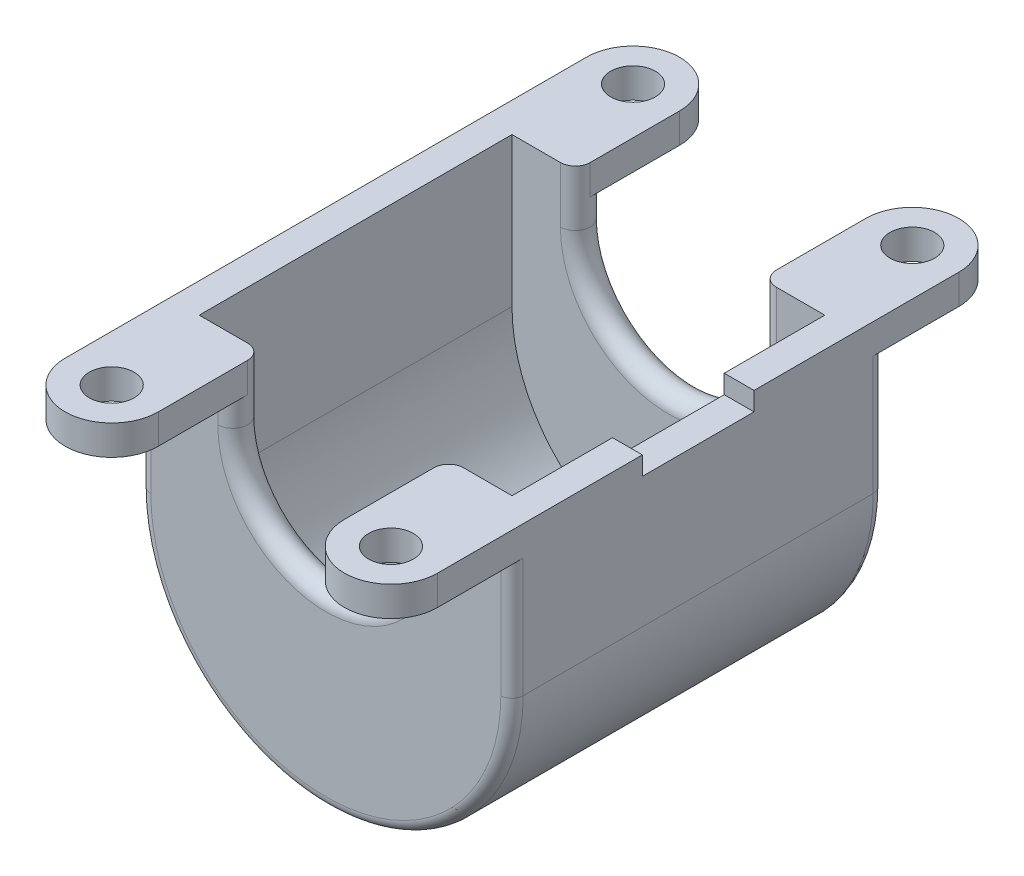
SolidWorks part; units mm, degrees
ref_plane "Alzado" through (0, 0, 0) normal (0, 0, 1) x (1, 0, 0)
ref_plane "Planta" through (0, 0, 0) normal (0, 1, 0) x (1, 0, 0)
ref_plane "Vista lateral" through (0, 0, 0) normal (1, 0, 0) x (0, 0, -1)
sketch "Croquis4" plane through (0, 0, 0) normal (0, 1, 0) x (1, 0, 0)
  line L0 (0, 0) -> (0, 140)
  line L1 (-25, 140) -> (-25, 120)
  line L2 (-25, 0) -> (-25, 20)
  line L3 (0, 70) -> (-100, 70) construction
  line L4 (-50, 70) -> (-50, 196) construction
  line L5 (-25, 120) -> (-75, 120)
  line L6 (-25, 20) -> (-75, 20)
  line L7 (-75, 0) -> (-75, 20)
  line L8 (-100, 0) -> (-100, 140)
  line L9 (-75, 140) -> (-75, 120)
  arc A0 (0, 140) -> (-25, 140) centre (-12.5, 140) ccw
  arc A1 (0, 0) -> (-25, 0) centre (-12.5, 0) cw
  arc A2 (-100, 0) -> (-75, 0) centre (-87.5, 0) ccw
  arc A3 (-100, 140) -> (-75, 140) centre (-87.5, 140) cw
  point P13 (0, 0)
  point P17 (-50, 20)
  point P24 (-50, 120)
  dimension "D2" = 12.5
  dimension "D1" = 140
  dimension "D3" = 100
  dimension "D4" = 50
  dimension "D5" = 50
extrude "Base" add sketch "Croquis4" along normal blind 8
sketch "Croquis5" plane through (0, 0, 0) normal (0, -1, 0) x (1, 0, 0)
  circle A0 centre (-87.5, 0) radius 6
  circle A1 centre (-12.5, 0) radius 6
  circle A2 centre (-87.5, -140) radius 6
  circle A3 centre (-12.5, -140) radius 6
  point P17 (-12.5, 0)
  point P21 (-87.5, -140)
  point P25 (-12.5, -140)
  dimension "D1" = 12
extrude "Perforaciones" cut sketch "Croquis5" against normal blind 8
ref_plane "Plano2" through (0, 0, -20) normal (0, 0, 1) x (1, 0, 0)
sketch "Croquis7" plane through (0, 0, -20) normal (0, 0, 1) x (1, 0, 0)
  line L1 (-100, 0) -> (-100, -32)
  line L2 (0, -32) -> (0, 0)
  line L4 (-50, -82) -> (-50, 14.9348) construction
  line L8 (-100, 0) -> (0, 0)
  arc A0 (-100, -32) -> (0, -32) centre (-50, -32) ccw
  dimension "D1" = 50
  dimension "D2" = 32
extrude "Saliente-Extruir5" add sketch "Croquis7" against normal blind 100
sketch "Croquis8" plane through (0, 8, 0) normal (0, 1, 0) x (1, 0, 0)
  line L2 (-100, 140) -> (-100, 0) construction
  line L3 (-92, 112) -> (-8, 112)
  line L4 (-92, 112) -> (-92, 28)
  line L5 (-92, 28) -> (-8, 28)
  line L6 (-8, 112) -> (-8, 28)
  line L7 (-25, 120) -> (-75, 120) construction
  line L8 (-26.0559, 20) -> (26.0559, 20) construction
  line L9 (0, 0) -> (0, 140) construction
  point P0 (0, 0)
  dimension "D1" = 8
  dimension "D2" = 8
  dimension "D3" = 8
  dimension "D4" = 8
shell "Vaciado2" thickness 8 removed face at (-12.5, 8, -6)
sketch "Croquis9" plane through (0, 0, -20) normal (0, 0, 1) x (1, 0, 0)
  line L0 (-75, 8) -> (-75, -7)
  line L1 (-25, -7) -> (-25, 8)
  line L2 (-25, 8) -> (-25, 0) construction
  line L3 (-25, 8) -> (-75, 8)
  arc A0 (-75, -7) -> (-25, -7) centre (-50, -7) ccw
  point P6 (-50, -32)
  point P10 (0, 0)
  dimension "D1" = 32
extrude "Cortar-Extruir3" cut sketch "Croquis9" against normal blind 100
sketch "Croquis10" plane through (0, 8, 0) normal (0, 1, 0) x (1, 0, 0)
  line L0 (-8, 55) -> (0, 55)
  line L1 (-8, 112) -> (-8, 28) construction
  line L2 (0, 0) -> (0, 140) construction
  line L3 (0, 55) -> (0, 85)
  line L4 (0, 85) -> (-8, 85)
  line L5 (-8, 85) -> (-8, 55)
  dimension "D1" = 30
  dimension "D2" = 27
extrude "Cortar-Extruir4" cut sketch "Croquis10" against normal blind 5
fillet "Redondeo1" 2 edges at (-50, -32, -20) (-50, -32, -28) type full round first side face at (-50, -19.125, -20) second side face at (-50, -14.125, -28) middle face at (-50, -19.5, -24)
fillet "Redondeo2" 2 edges at (-50, -32, -112) (-50, -32, -120) type full round first side face at (-50, -14.125, -112) second side face at (-50, -19.125, -120) middle face at (-50, -19.5, -116)
fillet "Redondeo3" radius 3 6 edges at (-100, -16, -120) (0, -16, -120) (-100, -16, -20) (0, -16, -20) (-50, -82, -120) (-50, -82, -20)
